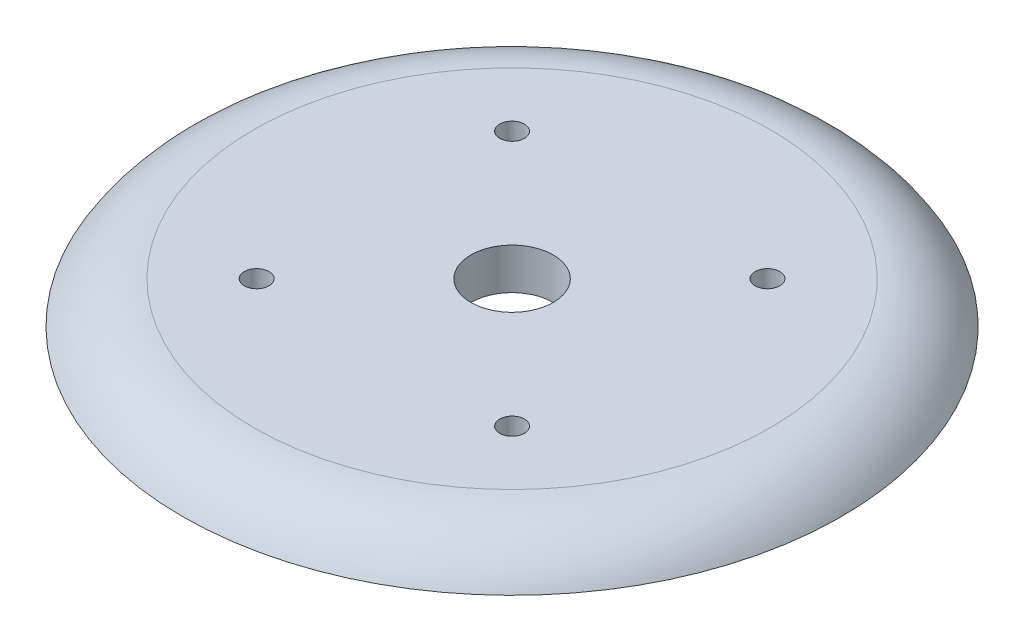
SolidWorks part; units mm, degrees
ref_plane "Front Plane" through (0, 0, 0) normal (0, 0, 1) x (1, 0, 0)
ref_plane "Top Plane" through (0, 0, 0) normal (0, 1, 0) x (1, 0, 0)
ref_plane "Right Plane" through (0, 0, 0) normal (1, 0, 0) x (0, 0, -1)
sketch "Sketch1" plane through (0, 0, 0) normal (0, 1, 0) x (1, 0, 0)
  line L1 (-15.5, 15.5) -> (15.5, 15.5)
  line L2 (-15.5, 15.5) -> (-15.5, -15.5)
  line L3 (-15.5, -15.5) -> (15.5, -15.5)
  line L4 (15.5, 15.5) -> (15.5, -15.5)
  line L5 (-15.5, 15.5) -> (15.5, -15.5) construction
  line L6 (-15.5, -15.5) -> (15.5, 15.5) construction
  circle A0 centre (0, 0) radius 40
  circle A1 centre (-15.5, 15.5) radius 1.5
  circle A2 centre (15.5, 15.5) radius 1.5
  circle A3 centre (-15.5, -15.5) radius 1.5
  circle A4 centre (15.5, -15.5) radius 1.5
  circle A5 centre (0, 0) radius 5
  dimension "D2" = 80
  dimension "D3" = 3
  dimension "D4" = 10
  dimension "D1" = 31
extrude "Boss-Extrude1" add sketch "Sketch1" along normal blind 5 contours A0 A4 L3 A3 L2 A1 L1 A2 L4 | A4 L4 A2 L1 A1 L2 A3 L3 region at (0, 0, -15.0616) region at (-38.8686, 0, 0)
fillet "Fillet2" radius 10 1 edges at (0, 5, 40)
